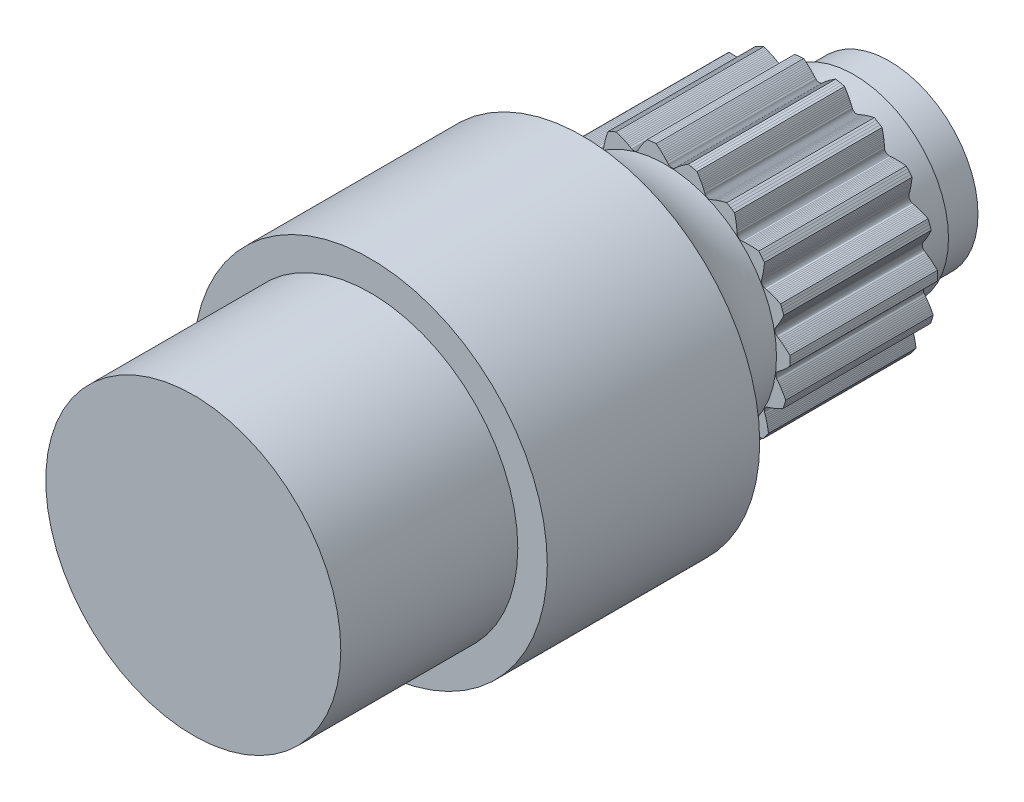
SolidWorks part; units mm, degrees
ref_plane "Front Plane" through (0, 0, 0) normal (0, 0, 1) x (1, 0, 0)
ref_plane "Top Plane" through (0, 0, 0) normal (0, 1, 0) x (1, 0, 0)
ref_plane "Right Plane" through (0, 0, 0) normal (1, 0, 0) x (0, 0, -1)
sketch "19T Shaft" plane through (0, 0, 0) normal (0, 0, 1) x (1, 0, 0)
  point P0 (-10.5755, 0)
  line B0 (6.0231, -8.6927) -> (5.8644, -8.8006)
  line B1 (5.8644, -8.8006) -> (5.7037, -8.9056)
  line B2 (5.7037, -8.9056) -> (5.5745, -8.8826)
  line B3 (5.5745, -8.8826) -> (5.4476, -8.8579)
  line B4 (5.4476, -8.8579) -> (5.3232, -8.8314)
  line B5 (5.3232, -8.8314) -> (5.1984, -8.8027)
  line B6 (5.1984, -8.8027) -> (5.0761, -8.7722)
  line B7 (5.0761, -8.7722) -> (4.9565, -8.7403)
  line B8 (4.9565, -8.7403) -> (4.8368, -8.706)
  line B9 (4.8368, -8.706) -> (4.7198, -8.6703)
  line B10 (4.7198, -8.6703) -> (4.603, -8.6323)
  line B11 (4.603, -8.6323) -> (4.4891, -8.593)
  line B12 (4.4891, -8.593) -> (4.3274, -8.5331)
  line B13 (4.3274, -8.5331) -> (4.2909, -8.5213)
  line B14 (4.2909, -8.5213) -> (4.254, -8.5136)
  line B15 (4.254, -8.5136) -> (4.2158, -8.5099)
  line B16 (4.2158, -8.5099) -> (4.1778, -8.5104)
  line B17 (4.1778, -8.5104) -> (4.1402, -8.515)
  line B18 (4.1402, -8.515) -> (4.1034, -8.5237)
  line B19 (4.1034, -8.5237) -> (4.0679, -8.5363)
  line B20 (4.0679, -8.5363) -> (4.0531, -8.5429)
  line B21 (4.0531, -8.5429) -> (4.0429, -8.5478)
  line B22 (4.0429, -8.5478) -> (4.0326, -8.5526)
  line B23 (4.0326, -8.5526) -> (4.0223, -8.5575)
  line B24 (4.0223, -8.5575) -> (4.012, -8.5623)
  line B25 (4.012, -8.5623) -> (3.9976, -8.5695)
  line B26 (3.9976, -8.5695) -> (3.9652, -8.5889)
  line B27 (3.9652, -8.5889) -> (3.9351, -8.6117)
  line B28 (3.9351, -8.6117) -> (3.9076, -8.6377)
  line B29 (3.9076, -8.6377) -> (3.883, -8.6668)
  line B30 (3.883, -8.6668) -> (3.8616, -8.6986)
  line B31 (3.8616, -8.6986) -> (3.8441, -8.732)
  line B32 (3.8441, -8.732) -> (3.83, -8.7676)
  line B33 (3.83, -8.7676) -> (3.7733, -8.9305)
  line B34 (3.7733, -8.9305) -> (3.7312, -9.0434)
  line B35 (3.7312, -9.0434) -> (3.6862, -9.1576)
  line B36 (3.6862, -9.1576) -> (3.6393, -9.2706)
  line B37 (3.6393, -9.2706) -> (3.5895, -9.3848)
  line B38 (3.5895, -9.3848) -> (3.5381, -9.4975)
  line B39 (3.5381, -9.4975) -> (3.4838, -9.6111)
  line B40 (3.4838, -9.6111) -> (3.4265, -9.7257)
  line B41 (3.4265, -9.7257) -> (3.3678, -9.8385)
  line B42 (3.3678, -9.8385) -> (3.3062, -9.9521)
  line B43 (3.3062, -9.9521) -> (3.2417, -10.0664)
  line B44 (3.2417, -10.0664) -> (3.0585, -10.1236)
  line B45 (3.0585, -10.1236) -> (2.8742, -10.1774)
  line B46 (8.5193, -6.266) -> (8.4042, -6.4196)
  line B47 (8.4042, -6.4196) -> (8.2863, -6.5711)
  line B48 (8.2863, -6.5711) -> (8.1566, -6.5913)
  line B49 (8.1566, -6.5913) -> (8.0286, -6.6091)
  line B50 (8.0286, -6.6091) -> (7.9024, -6.6245)
  line B51 (7.9024, -6.6245) -> (7.775, -6.6378)
  line B52 (7.775, -6.6378) -> (7.6495, -6.6487)
  line B53 (7.6495, -6.6487) -> (7.5259, -6.6573)
  line B54 (7.5259, -6.6573) -> (7.4015, -6.6638)
  line B55 (7.4015, -6.6638) -> (7.2793, -6.668)
  line B56 (7.2793, -6.668) -> (7.1565, -6.67)
  line B57 (7.1565, -6.67) -> (7.036, -6.6698)
  line B58 (7.036, -6.6698) -> (6.8636, -6.6657)
  line B59 (6.8636, -6.6657) -> (6.8253, -6.6663)
  line B60 (6.8253, -6.6663) -> (6.7879, -6.671)
  line B61 (6.7879, -6.671) -> (6.7506, -6.6799)
  line B62 (6.7506, -6.6799) -> (6.7147, -6.6927)
  line B63 (6.7147, -6.6927) -> (6.6807, -6.7093)
  line B64 (6.6807, -6.7093) -> (6.6487, -6.7295)
  line B65 (6.6487, -6.7295) -> (6.6192, -6.753)
  line B66 (6.6192, -6.753) -> (6.6074, -6.764)
  line B67 (6.6074, -6.764) -> (6.5993, -6.7719)
  line B68 (6.5993, -6.7719) -> (6.5911, -6.7798)
  line B69 (6.5911, -6.7798) -> (6.583, -6.7878)
  line B70 (6.583, -6.7878) -> (6.5748, -6.7957)
  line B71 (6.5748, -6.7957) -> (6.5635, -6.8072)
  line B72 (6.5635, -6.8072) -> (6.5392, -6.836)
  line B73 (6.5392, -6.836) -> (6.5181, -6.8673)
  line B74 (6.5181, -6.8673) -> (6.5006, -6.9009)
  line B75 (6.5006, -6.9009) -> (6.4867, -6.9364)
  line B76 (6.4867, -6.9364) -> (6.4768, -6.9734)
  line B77 (6.4768, -6.9734) -> (6.4711, -7.0107)
  line B78 (6.4711, -7.0107) -> (6.4693, -7.049)
  line B79 (6.4693, -7.049) -> (6.4686, -7.2215)
  line B80 (6.4686, -7.2215) -> (6.4654, -7.3419)
  line B81 (6.4654, -7.3419) -> (6.4599, -7.4646)
  line B82 (6.4599, -7.4646) -> (6.4523, -7.5866)
  line B83 (6.4523, -7.5866) -> (6.4423, -7.7108)
  line B84 (6.4423, -7.7108) -> (6.4302, -7.834)
  line B85 (6.4302, -7.834) -> (6.4157, -7.9592)
  line B86 (6.4157, -7.9592) -> (6.3988, -8.0862)
  line B87 (6.3988, -8.0862) -> (6.3799, -8.2119)
  line B88 (6.3799, -8.2119) -> (6.3585, -8.3394)
  line B89 (6.3585, -8.3394) -> (6.3346, -8.4684)
  line B90 (6.3346, -8.4684) -> (6.1799, -8.582)
  line B91 (6.1799, -8.582) -> (6.0231, -8.6927)
  line B92 (10.0923, -3.1603) -> (10.0332, -3.3429)
  line B93 (10.0332, -3.3429) -> (9.9709, -3.5245)
  line B94 (9.9709, -3.5245) -> (9.8549, -3.5857)
  line B95 (9.8549, -3.5857) -> (9.7396, -3.6441)
  line B96 (9.7396, -3.6441) -> (9.6252, -3.6997)
  line B97 (9.6252, -3.6997) -> (9.509, -3.7536)
  line B98 (9.509, -3.7536) -> (9.3938, -3.8047)
  line B99 (9.3938, -3.8047) -> (9.2797, -3.853)
  line B100 (9.2797, -3.853) -> (9.1642, -3.8995)
  line B101 (9.1642, -3.8995) -> (9.05, -3.9431)
  line B102 (9.05, -3.9431) -> (8.9345, -3.9849)
  line B103 (8.9345, -3.9849) -> (8.8205, -4.0238)
  line B104 (8.8205, -4.0238) -> (8.6561, -4.0759)
  line B105 (8.6561, -4.0759) -> (8.62, -4.089)
  line B106 (8.62, -4.089) -> (8.5862, -4.1055)
  line B107 (8.5862, -4.1055) -> (8.5538, -4.1261)
  line B108 (8.5538, -4.1261) -> (8.524, -4.1498)
  line B109 (8.524, -4.1498) -> (8.4972, -4.1766)
  line B110 (8.4972, -4.1766) -> (8.4735, -4.206)
  line B111 (8.4735, -4.206) -> (8.4533, -4.2378)
  line B112 (8.4533, -4.2378) -> (8.4457, -4.2521)
  line B113 (8.4457, -4.2521) -> (8.4405, -4.2622)
  line B114 (8.4405, -4.2622) -> (8.4354, -4.2723)
  line B115 (8.4354, -4.2723) -> (8.4303, -4.2825)
  line B116 (8.4303, -4.2825) -> (8.4251, -4.2926)
  line B117 (8.4251, -4.2926) -> (8.4181, -4.3072)
  line B118 (8.4181, -4.3072) -> (8.4045, -4.3423)
  line B119 (8.4045, -4.3423) -> (8.3948, -4.3788)
  line B120 (8.3948, -4.3788) -> (8.3891, -4.4163)
  line B121 (8.3891, -4.4163) -> (8.3875, -4.4543)
  line B122 (8.3875, -4.4543) -> (8.3902, -4.4926)
  line B123 (8.3902, -4.4926) -> (8.3968, -4.5297)
  line B124 (8.3968, -4.5297) -> (8.4076, -4.5665)
  line B125 (8.4076, -4.5665) -> (8.4629, -4.7298)
  line B126 (8.4629, -4.7298) -> (8.499, -4.8448)
  line B127 (8.499, -4.8448) -> (8.5336, -4.9626)
  line B128 (8.5336, -4.9626) -> (8.566, -5.0805)
  line B129 (8.566, -5.0805) -> (8.5969, -5.2012)
  line B130 (8.5969, -5.2012) -> (8.6255, -5.3217)
  line B131 (8.6255, -5.3217) -> (8.6525, -5.4448)
  line B132 (8.6525, -5.4448) -> (8.6777, -5.5704)
  line B133 (8.6777, -5.5704) -> (8.7006, -5.6954)
  line B134 (8.7006, -5.6954) -> (8.7218, -5.8229)
  line B135 (8.7218, -5.8229) -> (8.7411, -5.9527)
  line B136 (8.7411, -5.9527) -> (8.6316, -6.1104)
  line B137 (8.6316, -6.1104) -> (8.5193, -6.266)
  line B138 (10.5716, 0.2879) -> (10.5751, 0.096)
  line B139 (10.5751, 0.096) -> (10.5751, -0.096)
  line B140 (10.5751, -0.096) -> (10.4852, -0.1916)
  line B141 (10.4852, -0.1916) -> (10.3951, -0.2842)
  line B142 (10.3951, -0.2842) -> (10.3049, -0.3739)
  line B143 (10.3049, -0.3739) -> (10.2126, -0.4627)
  line B144 (10.2126, -0.4627) -> (10.1202, -0.5484)
  line B145 (10.1202, -0.5484) -> (10.028, -0.6311)
  line B146 (10.028, -0.6311) -> (9.9338, -0.7126)
  line B147 (9.9338, -0.7126) -> (9.8399, -0.791)
  line B148 (9.8399, -0.791) -> (9.7443, -0.868)
  line B149 (9.7443, -0.868) -> (9.6491, -0.9418)
  line B150 (9.6491, -0.9418) -> (9.5105, -1.0445)
  line B151 (9.5105, -1.0445) -> (9.4807, -1.0685)
  line B152 (9.4807, -1.0685) -> (9.454, -1.0952)
  line B153 (9.454, -1.0952) -> (9.43, -1.1251)
  line B154 (9.43, -1.1251) -> (9.4096, -1.1573)
  line B155 (9.4096, -1.1573) -> (9.3929, -1.1913)
  line B156 (9.3929, -1.1913) -> (9.3801, -1.2268)
  line B157 (9.3801, -1.2268) -> (9.3712, -1.2634)
  line B158 (9.3712, -1.2634) -> (9.3687, -1.2794)
  line B159 (9.3687, -1.2794) -> (9.3671, -1.2906)
  line B160 (9.3671, -1.2906) -> (9.3656, -1.3019)
  line B161 (9.3656, -1.3019) -> (9.364, -1.3131)
  line B162 (9.364, -1.3131) -> (9.3624, -1.3244)
  line B163 (9.3624, -1.3244) -> (9.3605, -1.3404)
  line B164 (9.3605, -1.3404) -> (9.3591, -1.3781)
  line B165 (9.3591, -1.3781) -> (9.3617, -1.4158)
  line B166 (9.3617, -1.4158) -> (9.3685, -1.4531)
  line B167 (9.3685, -1.4531) -> (9.3794, -1.4895)
  line B168 (9.3794, -1.4895) -> (9.3943, -1.5249)
  line B169 (9.3943, -1.5249) -> (9.4126, -1.5578)
  line B170 (9.4126, -1.5578) -> (9.4348, -1.5891)
  line B171 (9.4348, -1.5891) -> (9.5401, -1.7256)
  line B172 (9.5401, -1.7256) -> (9.6116, -1.8226)
  line B173 (9.6116, -1.8226) -> (9.6826, -1.9228)
  line B174 (9.6826, -1.9228) -> (9.7515, -2.0239)
  line B175 (9.7515, -2.0239) -> (9.8199, -2.128)
  line B176 (9.8199, -2.128) -> (9.8861, -2.2327)
  line B177 (9.8861, -2.2327) -> (9.9516, -2.3403)
  line B178 (9.9516, -2.3403) -> (10.0162, -2.4509)
  line B179 (10.0162, -2.4509) -> (10.0785, -2.5618)
  line B180 (10.0785, -2.5618) -> (10.1399, -2.6755)
  line B181 (10.1399, -2.6755) -> (10.2003, -2.792)
  line B182 (10.2003, -2.792) -> (10.1479, -2.9766)
  line B183 (10.1479, -2.9766) -> (10.0923, -3.1603)
  line B184 (9.9053, 3.7049) -> (9.9709, 3.5245)
  line B185 (9.9709, 3.5245) -> (10.0332, 3.3429)
  line B186 (10.0332, 3.3429) -> (9.9793, 3.2233)
  line B187 (9.9793, 3.2233) -> (9.9242, 3.1065)
  line B188 (9.9242, 3.1065) -> (9.868, 2.9924)
  line B189 (9.868, 2.9924) -> (9.8094, 2.8784)
  line B190 (9.8094, 2.8784) -> (9.7499, 2.7674)
  line B191 (9.7499, 2.7674) -> (9.6896, 2.6592)
  line B192 (9.6896, 2.6592) -> (9.627, 2.5516)
  line B193 (9.627, 2.5516) -> (9.5636, 2.4469)
  line B194 (9.5636, 2.4469) -> (9.4981, 2.343)
  line B195 (9.4981, 2.343) -> (9.4321, 2.2423)
  line B196 (9.4321, 2.2423) -> (9.3343, 2.1002)
  line B197 (9.3343, 2.1002) -> (9.3139, 2.0678)
  line B198 (9.3139, 2.0678) -> (9.2974, 2.0339)
  line B199 (9.2974, 2.0339) -> (9.2844, 1.9978)
  line B200 (9.2844, 1.9978) -> (9.2755, 1.9607)
  line B201 (9.2755, 1.9607) -> (9.2708, 1.9232)
  line B202 (9.2708, 1.9232) -> (9.2702, 1.8854)
  line B203 (9.2702, 1.8854) -> (9.2737, 1.8479)
  line B204 (9.2737, 1.8479) -> (9.2765, 1.832)
  line B205 (9.2765, 1.832) -> (9.2787, 1.8208)
  line B206 (9.2787, 1.8208) -> (9.2809, 1.8097)
  line B207 (9.2809, 1.8097) -> (9.283, 1.7985)
  line B208 (9.283, 1.7985) -> (9.2852, 1.7873)
  line B209 (9.2852, 1.7873) -> (9.2886, 1.7716)
  line B210 (9.2886, 1.7716) -> (9.2994, 1.7354)
  line B211 (9.2994, 1.7354) -> (9.3142, 1.7007)
  line B212 (9.3142, 1.7007) -> (9.3327, 1.6676)
  line B213 (9.3327, 1.6676) -> (9.3548, 1.6366)
  line B214 (9.3548, 1.6366) -> (9.3804, 1.6081)
  line B215 (9.3804, 1.6081) -> (9.4085, 1.5829)
  line B216 (9.4085, 1.5829) -> (9.4396, 1.5605)
  line B217 (9.4396, 1.5605) -> (9.5835, 1.4655)
  line B218 (9.5835, 1.4655) -> (9.6826, 1.397)
  line B219 (9.6826, 1.397) -> (9.7823, 1.3253)
  line B220 (9.7823, 1.3253) -> (9.8803, 1.2521)
  line B221 (9.8803, 1.2521) -> (9.9788, 1.1759)
  line B222 (9.9788, 1.1759) -> (10.0754, 1.0983)
  line B223 (10.0754, 1.0983) -> (10.1722, 1.0178)
  line B224 (10.1722, 1.0178) -> (10.2693, 0.9342)
  line B225 (10.2693, 0.9342) -> (10.3642, 0.8495)
  line B226 (10.3642, 0.8495) -> (10.4592, 0.7619)
  line B227 (10.4592, 0.7619) -> (10.5542, 0.6713)
  line B228 (10.5542, 0.6713) -> (10.5646, 0.4797)
  line B229 (10.5646, 0.4797) -> (10.5716, 0.2879)
  line B230 (8.1656, 6.7204) -> (8.2863, 6.5711)
  line B231 (8.2863, 6.5711) -> (8.4042, 6.4196)
  line B232 (8.4042, 6.4196) -> (8.392, 6.2889)
  line B233 (8.392, 6.2889) -> (8.3778, 6.1605)
  line B234 (8.3778, 6.1605) -> (8.3617, 6.0344)
  line B235 (8.3617, 6.0344) -> (8.3433, 5.9076)
  line B236 (8.3433, 5.9076) -> (8.3231, 5.7832)
  line B237 (8.3231, 5.7832) -> (8.3011, 5.6613)
  line B238 (8.3011, 5.6613) -> (8.2769, 5.5392)
  line B239 (8.2769, 5.5392) -> (8.2509, 5.4196)
  line B240 (8.2509, 5.4196) -> (8.2227, 5.3001)
  line B241 (8.2227, 5.3001) -> (8.193, 5.1834)
  line B242 (8.193, 5.1834) -> (8.1466, 5.0172)
  line B243 (8.1466, 5.0172) -> (8.1379, 4.9799)
  line B244 (8.1379, 4.9799) -> (8.1332, 4.9425)
  line B245 (8.1332, 4.9425) -> (8.1327, 4.9042)
  line B246 (8.1327, 4.9042) -> (8.1363, 4.8663)
  line B247 (8.1363, 4.8663) -> (8.144, 4.8292)
  line B248 (8.144, 4.8292) -> (8.1557, 4.7933)
  line B249 (8.1557, 4.7933) -> (8.1712, 4.7589)
  line B250 (8.1712, 4.7589) -> (8.179, 4.7448)
  line B251 (8.179, 4.7448) -> (8.1847, 4.7349)
  line B252 (8.1847, 4.7349) -> (8.1904, 4.7251)
  line B253 (8.1904, 4.7251) -> (8.1961, 4.7152)
  line B254 (8.1961, 4.7152) -> (8.2017, 4.7054)
  line B255 (8.2017, 4.7054) -> (8.2101, 4.6916)
  line B256 (8.2101, 4.6916) -> (8.2321, 4.6609)
  line B257 (8.2321, 4.6609) -> (8.2573, 4.6328)
  line B258 (8.2573, 4.6328) -> (8.2855, 4.6076)
  line B259 (8.2855, 4.6076) -> (8.3165, 4.5855)
  line B260 (8.3165, 4.5855) -> (8.35, 4.5667)
  line B261 (8.35, 4.5667) -> (8.3847, 4.552)
  line B262 (8.3847, 4.552) -> (8.4214, 4.541)
  line B263 (8.4214, 4.541) -> (8.5884, 4.4979)
  line B264 (8.5884, 4.4979) -> (8.7044, 4.4652)
  line B265 (8.7044, 4.4652) -> (8.822, 4.4298)
  line B266 (8.822, 4.4298) -> (8.9384, 4.3924)
  line B267 (8.9384, 4.3924) -> (9.0563, 4.3523)
  line B268 (9.0563, 4.3523) -> (9.1728, 4.3103)
  line B269 (9.1728, 4.3103) -> (9.2906, 4.2655)
  line B270 (9.2906, 4.2655) -> (9.4096, 4.218)
  line B271 (9.4096, 4.218) -> (9.5268, 4.1688)
  line B272 (9.5268, 4.1688) -> (9.6451, 4.1167)
  line B273 (9.6451, 4.1167) -> (9.7643, 4.0619)
  line B274 (9.7643, 4.0619) -> (9.8364, 3.884)
  line B275 (9.8364, 3.884) -> (9.9053, 3.7049)
  line B276 (5.5411, 9.0076) -> (5.7037, 8.9056)
  line B277 (5.7037, 8.9056) -> (5.8644, 8.8006)
  line B278 (5.8644, 8.8006) -> (5.8952, 8.6731)
  line B279 (5.8952, 8.6731) -> (5.9235, 8.547)
  line B280 (5.9235, 8.547) -> (5.9493, 8.4224)
  line B281 (5.9493, 8.4224) -> (5.9731, 8.2966)
  line B282 (5.9731, 8.2966) -> (5.9943, 8.1724)
  line B283 (5.9943, 8.1724) -> (6.0131, 8.0499)
  line B284 (6.0131, 8.0499) -> (6.0298, 7.9265)
  line B285 (6.0298, 7.9265) -> (6.0441, 7.8051)
  line B286 (6.0441, 7.8051) -> (6.0563, 7.6829)
  line B287 (6.0563, 7.6829) -> (6.066, 7.5628)
  line B288 (6.066, 7.5628) -> (6.0761, 7.3906)
  line B289 (6.0761, 7.3906) -> (6.0799, 7.3525)
  line B290 (6.0799, 7.3525) -> (6.0877, 7.3156)
  line B291 (6.0877, 7.3156) -> (6.0996, 7.2791)
  line B292 (6.0996, 7.2791) -> (6.1154, 7.2445)
  line B293 (6.1154, 7.2445) -> (6.1347, 7.2119)
  line B294 (6.1347, 7.2119) -> (6.1575, 7.1817)
  line B295 (6.1575, 7.1817) -> (6.1833, 7.1543)
  line B296 (6.1833, 7.1543) -> (6.1952, 7.1434)
  line B297 (6.1952, 7.1434) -> (6.2038, 7.1359)
  line B298 (6.2038, 7.1359) -> (6.2124, 7.1285)
  line B299 (6.2124, 7.1285) -> (6.221, 7.121)
  line B300 (6.221, 7.121) -> (6.2295, 7.1135)
  line B301 (6.2295, 7.1135) -> (6.2419, 7.1032)
  line B302 (6.2419, 7.1032) -> (6.2726, 7.0813)
  line B303 (6.2726, 7.0813) -> (6.3056, 7.063)
  line B304 (6.3056, 7.063) -> (6.3405, 7.0482)
  line B305 (6.3405, 7.0482) -> (6.377, 7.0374)
  line B306 (6.377, 7.0374) -> (6.4148, 7.0305)
  line B307 (6.4148, 7.0305) -> (6.4524, 7.0279)
  line B308 (6.4524, 7.0279) -> (6.4907, 7.0293)
  line B309 (6.4907, 7.0293) -> (6.6626, 7.0428)
  line B310 (6.6626, 7.0428) -> (6.7829, 7.0496)
  line B311 (6.7829, 7.0496) -> (6.9056, 7.0543)
  line B312 (6.9056, 7.0543) -> (7.0279, 7.0567)
  line B313 (7.0279, 7.0567) -> (7.1524, 7.057)
  line B314 (7.1524, 7.057) -> (7.2763, 7.0552)
  line B315 (7.2763, 7.0552) -> (7.4022, 7.0511)
  line B316 (7.4022, 7.0511) -> (7.5302, 7.0447)
  line B317 (7.5302, 7.0447) -> (7.657, 7.0362)
  line B318 (7.657, 7.0362) -> (7.7858, 7.0255)
  line B319 (7.7858, 7.0255) -> (7.9164, 7.0123)
  line B320 (7.9164, 7.0123) -> (8.0423, 6.8675)
  line B321 (8.0423, 6.8675) -> (8.1656, 6.7204)
  line B322 (2.3161, 10.3188) -> (2.503, 10.275)
  line B323 (2.503, 10.275) -> (2.6891, 10.2279)
  line B324 (2.6891, 10.2279) -> (2.7597, 10.1173)
  line B325 (2.7597, 10.1173) -> (2.8274, 10.0073)
  line B326 (2.8274, 10.0073) -> (2.8922, 9.8978)
  line B327 (2.8922, 9.8978) -> (2.9555, 9.7865)
  line B328 (2.9555, 9.7865) -> (3.016, 9.6759)
  line B329 (3.016, 9.6759) -> (3.0735, 9.5662)
  line B330 (3.0735, 9.5662) -> (3.1294, 9.4549)
  line B331 (3.1294, 9.4549) -> (3.1823, 9.3447)
  line B332 (3.1823, 9.3447) -> (3.2335, 9.233)
  line B333 (3.2335, 9.233) -> (3.2817, 9.1226)
  line B334 (3.2817, 9.1226) -> (3.3472, 8.9631)
  line B335 (3.3472, 8.9631) -> (3.3632, 8.9283)
  line B336 (3.3632, 8.9283) -> (3.3825, 8.8959)
  line B337 (3.3825, 8.8959) -> (3.4056, 8.8653)
  line B338 (3.4056, 8.8653) -> (3.4318, 8.8376)
  line B339 (3.4318, 8.8376) -> (3.4606, 8.8131)
  line B340 (3.4606, 8.8131) -> (3.4919, 8.7919)
  line B341 (3.4919, 8.7919) -> (3.5253, 8.7743)
  line B342 (3.5253, 8.7743) -> (3.5401, 8.7679)
  line B343 (3.5401, 8.7679) -> (3.5506, 8.7637)
  line B344 (3.5506, 8.7637) -> (3.5612, 8.7594)
  line B345 (3.5612, 8.7594) -> (3.5717, 8.7551)
  line B346 (3.5717, 8.7551) -> (3.5822, 8.7508)
  line B347 (3.5822, 8.7508) -> (3.5973, 8.7451)
  line B348 (3.5973, 8.7451) -> (3.6335, 8.7344)
  line B349 (3.6335, 8.7344) -> (3.6706, 8.7277)
  line B350 (3.6706, 8.7277) -> (3.7084, 8.7251)
  line B351 (3.7084, 8.7251) -> (3.7465, 8.7267)
  line B352 (3.7465, 8.7267) -> (3.7844, 8.7325)
  line B353 (3.7844, 8.7325) -> (3.8208, 8.7422)
  line B354 (3.8208, 8.7422) -> (3.8566, 8.756)
  line B355 (3.8566, 8.756) -> (4.0148, 8.8246)
  line B356 (4.0148, 8.8246) -> (4.1264, 8.87)
  line B357 (4.1264, 8.87) -> (4.2409, 8.9143)
  line B358 (4.2409, 8.9143) -> (4.3558, 8.9563)
  line B359 (4.3558, 8.9563) -> (4.4735, 8.997)
  line B360 (4.4735, 8.997) -> (4.5912, 9.0355)
  line B361 (4.5912, 9.0355) -> (4.7116, 9.0725)
  line B362 (4.7116, 9.0725) -> (4.8347, 9.1081)
  line B363 (4.8347, 9.1081) -> (4.9575, 9.1412)
  line B364 (4.9575, 9.1412) -> (5.0828, 9.1728)
  line B365 (5.0828, 9.1728) -> (5.2106, 9.2028)
  line B366 (5.2106, 9.2028) -> (5.3767, 9.1067)
  line B367 (5.3767, 9.1067) -> (5.5411, 9.0076)
  line B368 (-1.1599, 10.5117) -> (-0.9689, 10.531)
  line B369 (-0.9689, 10.531) -> (-0.7776, 10.5469)
  line B370 (-0.7776, 10.5469) -> (-0.6749, 10.4652)
  line B371 (-0.6749, 10.4652) -> (-0.5752, 10.3831)
  line B372 (-0.5752, 10.3831) -> (-0.4783, 10.3006)
  line B373 (-0.4783, 10.3006) -> (-0.3823, 10.2159)
  line B374 (-0.3823, 10.2159) -> (-0.2892, 10.1309)
  line B375 (-0.2892, 10.1309) -> (-0.1992, 10.0459)
  line B376 (-0.1992, 10.0459) -> (-0.1102, 9.9587)
  line B377 (-0.1102, 9.9587) -> (-0.0243, 9.8716)
  line B378 (-0.0243, 9.8716) -> (0.0603, 9.7827)
  line B379 (0.0603, 9.7827) -> (0.1418, 9.6939)
  line B380 (0.1418, 9.6939) -> (0.2555, 9.5643)
  line B381 (0.2555, 9.5643) -> (0.2819, 9.5365)
  line B382 (0.2819, 9.5365) -> (0.3107, 9.5122)
  line B383 (0.3107, 9.5122) -> (0.3425, 9.4907)
  line B384 (0.3425, 9.4907) -> (0.3763, 9.473)
  line B385 (0.3763, 9.473) -> (0.4115, 9.4592)
  line B386 (0.4115, 9.4592) -> (0.448, 9.4494)
  line B387 (0.448, 9.4494) -> (0.4852, 9.4436)
  line B388 (0.4852, 9.4436) -> (0.5013, 9.4423)
  line B389 (0.5013, 9.4423) -> (0.5127, 9.4417)
  line B390 (0.5127, 9.4417) -> (0.524, 9.4411)
  line B391 (0.524, 9.4411) -> (0.5354, 9.4405)
  line B392 (0.5354, 9.4405) -> (0.5467, 9.4398)
  line B393 (0.5467, 9.4398) -> (0.5629, 9.4393)
  line B394 (0.5629, 9.4393) -> (0.6005, 9.4409)
  line B395 (0.6005, 9.4409) -> (0.6379, 9.4467)
  line B396 (0.6379, 9.4467) -> (0.6744, 9.4565)
  line B397 (0.6744, 9.4565) -> (0.7099, 9.4703)
  line B398 (0.7099, 9.4703) -> (0.7439, 9.4881)
  line B399 (0.7439, 9.4881) -> (0.7752, 9.5091)
  line B400 (0.7752, 9.5091) -> (0.8045, 9.5338)
  line B401 (0.8045, 9.5338) -> (0.9319, 9.6501)
  line B402 (0.9319, 9.6501) -> (1.0227, 9.7293)
  line B403 (1.0227, 9.7293) -> (1.1167, 9.8083)
  line B404 (1.1167, 9.8083) -> (1.2117, 9.8854)
  line B405 (1.2117, 9.8854) -> (1.3098, 9.9621)
  line B406 (1.3098, 9.9621) -> (1.4086, 10.0367)
  line B407 (1.4086, 10.0367) -> (1.5105, 10.1108)
  line B408 (1.5105, 10.1108) -> (1.6154, 10.1844)
  line B409 (1.6154, 10.1844) -> (1.7207, 10.2556)
  line B410 (1.7207, 10.2556) -> (1.829, 10.3262)
  line B411 (1.829, 10.3262) -> (1.9401, 10.396)
  line B412 (1.9401, 10.396) -> (2.1285, 10.3591)
  line B413 (2.1285, 10.3591) -> (2.3161, 10.3188)
  line B414 (-4.5102, 9.5655) -> (-4.3358, 9.6458)
  line B415 (-4.3358, 9.6458) -> (-4.1601, 9.7229)
  line B416 (-4.1601, 9.7229) -> (-4.0364, 9.679)
  line B417 (-4.0364, 9.679) -> (-3.9154, 9.6337)
  line B418 (-3.9154, 9.6337) -> (-3.797, 9.5872)
  line B419 (-3.797, 9.5872) -> (-3.6786, 9.5382)
  line B420 (-3.6786, 9.5382) -> (-3.5631, 9.4881)
  line B421 (-3.5631, 9.4881) -> (-3.4503, 9.4369)
  line B422 (-3.4503, 9.4369) -> (-3.3378, 9.3834)
  line B423 (-3.3378, 9.3834) -> (-3.2283, 9.3289)
  line B424 (-3.2283, 9.3289) -> (-3.1194, 9.2722)
  line B425 (-3.1194, 9.2722) -> (-3.0135, 9.2147)
  line B426 (-3.0135, 9.2147) -> (-2.8638, 9.129)
  line B427 (-2.8638, 9.129) -> (-2.8298, 9.1113)
  line B428 (-2.8298, 9.1113) -> (-2.7947, 9.0977)
  line B429 (-2.7947, 9.0977) -> (-2.7577, 9.0877)
  line B430 (-2.7577, 9.0877) -> (-2.72, 9.0819)
  line B431 (-2.72, 9.0819) -> (-2.6822, 9.0803)
  line B432 (-2.6822, 9.0803) -> (-2.6445, 9.0828)
  line B433 (-2.6445, 9.0828) -> (-2.6074, 9.0894)
  line B434 (-2.6074, 9.0894) -> (-2.5917, 9.0935)
  line B435 (-2.5917, 9.0935) -> (-2.5808, 9.0966)
  line B436 (-2.5808, 9.0966) -> (-2.5699, 9.0997)
  line B437 (-2.5699, 9.0997) -> (-2.5589, 9.1028)
  line B438 (-2.5589, 9.1028) -> (-2.548, 9.1059)
  line B439 (-2.548, 9.1059) -> (-2.5325, 9.1106)
  line B440 (-2.5325, 9.1106) -> (-2.4975, 9.1244)
  line B441 (-2.4975, 9.1244) -> (-2.464, 9.1419)
  line B442 (-2.464, 9.1419) -> (-2.4326, 9.1631)
  line B443 (-2.4326, 9.1631) -> (-2.4036, 9.1877)
  line B444 (-2.4036, 9.1877) -> (-2.3772, 9.2156)
  line B445 (-2.3772, 9.2156) -> (-2.3544, 9.2456)
  line B446 (-2.3544, 9.2456) -> (-2.3347, 9.2785)
  line B447 (-2.3347, 9.2785) -> (-2.2519, 9.4298)
  line B448 (-2.2519, 9.4298) -> (-2.1918, 9.5342)
  line B449 (-2.1918, 9.5342) -> (-2.1286, 9.6395)
  line B450 (-2.1286, 9.6395) -> (-2.0638, 9.7432)
  line B451 (-2.0638, 9.7432) -> (-1.9959, 9.8476)
  line B452 (-1.9959, 9.8476) -> (-1.9266, 9.9503)
  line B453 (-1.9266, 9.9503) -> (-1.8543, 10.0535)
  line B454 (-1.8543, 10.0535) -> (-1.779, 10.1571)
  line B455 (-1.779, 10.1571) -> (-1.7025, 10.2587)
  line B456 (-1.7025, 10.2587) -> (-1.623, 10.3606)
  line B457 (-1.623, 10.3606) -> (-1.5406, 10.4627)
  line B458 (-1.5406, 10.4627) -> (-1.3505, 10.4889)
  line B459 (-1.3505, 10.4889) -> (-1.1599, 10.5117)
  line B460 (-7.3717, 7.5828) -> (-7.2329, 7.7153)
  line B461 (-7.2329, 7.7153) -> (-7.0917, 7.8453)
  line B462 (-7.0917, 7.8453) -> (-6.9605, 7.844)
  line B463 (-6.9605, 7.844) -> (-6.8313, 7.8404)
  line B464 (-6.8313, 7.8404) -> (-6.7042, 7.8348)
  line B465 (-6.7042, 7.8348) -> (-6.5764, 7.827)
  line B466 (-6.5764, 7.827) -> (-6.4508, 7.8171)
  line B467 (-6.4508, 7.8171) -> (-6.3275, 7.8052)
  line B468 (-6.3275, 7.8052) -> (-6.2037, 7.7912)
  line B469 (-6.2037, 7.7912) -> (-6.0825, 7.7752)
  line B470 (-6.0825, 7.7752) -> (-5.961, 7.757)
  line B471 (-5.961, 7.757) -> (-5.8422, 7.7369)
  line B472 (-5.8422, 7.7369) -> (-5.6729, 7.7045)
  line B473 (-5.6729, 7.7045) -> (-5.635, 7.6988)
  line B474 (-5.635, 7.6988) -> (-5.5973, 7.6973)
  line B475 (-5.5973, 7.6973) -> (-5.559, 7.6999)
  line B476 (-5.559, 7.6999) -> (-5.5215, 7.7067)
  line B477 (-5.5215, 7.7067) -> (-5.4852, 7.7174)
  line B478 (-5.4852, 7.7174) -> (-5.4504, 7.732)
  line B479 (-5.4504, 7.732) -> (-5.4174, 7.7503)
  line B480 (-5.4174, 7.7503) -> (-5.404, 7.7593)
  line B481 (-5.404, 7.7593) -> (-5.3946, 7.7658)
  line B482 (-5.3946, 7.7658) -> (-5.3853, 7.7722)
  line B483 (-5.3853, 7.7722) -> (-5.376, 7.7787)
  line B484 (-5.376, 7.7787) -> (-5.3666, 7.7852)
  line B485 (-5.3666, 7.7852) -> (-5.3535, 7.7946)
  line B486 (-5.3535, 7.7946) -> (-5.3248, 7.8191)
  line B487 (-5.3248, 7.8191) -> (-5.2989, 7.8465)
  line B488 (-5.2989, 7.8465) -> (-5.2761, 7.8768)
  line B489 (-5.2761, 7.8768) -> (-5.2566, 7.9095)
  line B490 (-5.2566, 7.9095) -> (-5.2407, 7.9444)
  line B491 (-5.2407, 7.9444) -> (-5.2289, 7.9802)
  line B492 (-5.2289, 7.9802) -> (-5.2209, 8.0177)
  line B493 (-5.2209, 8.0177) -> (-5.1918, 8.1877)
  line B494 (-5.1918, 8.1877) -> (-5.1688, 8.3059)
  line B495 (-5.1688, 8.3059) -> (-5.1432, 8.426)
  line B496 (-5.1432, 8.426) -> (-5.1155, 8.5452)
  line B497 (-5.1155, 8.5452) -> (-5.0853, 8.666)
  line B498 (-5.0853, 8.666) -> (-5.0531, 8.7856)
  line B499 (-5.0531, 8.7856) -> (-5.0182, 8.9066)
  line B500 (-5.0182, 8.9066) -> (-4.9806, 9.0291)
  line B501 (-4.9806, 9.0291) -> (-4.9412, 9.15)
  line B502 (-4.9412, 9.15) -> (-4.8992, 9.2722)
  line B503 (-4.8992, 9.2722) -> (-4.8544, 9.3956)
  line B504 (-4.8544, 9.3956) -> (-4.683, 9.4821)
  line B505 (-4.683, 9.4821) -> (-4.5102, 9.5655)
  line B506 (-9.4344, 4.7783) -> (-9.3462, 4.9488)
  line B507 (-9.3462, 4.9488) -> (-9.2548, 5.1176)
  line B508 (-9.2548, 5.1176) -> (-9.1303, 5.1589)
  line B509 (-9.1303, 5.1589) -> (-9.007, 5.1975)
  line B510 (-9.007, 5.1975) -> (-8.885, 5.2334)
  line B511 (-8.885, 5.2334) -> (-8.7615, 5.2675)
  line B512 (-8.7615, 5.2675) -> (-8.6395, 5.299)
  line B513 (-8.6395, 5.299) -> (-8.519, 5.3278)
  line B514 (-8.519, 5.3278) -> (-8.3974, 5.3547)
  line B515 (-8.3974, 5.3547) -> (-8.2775, 5.3789)
  line B516 (-8.2775, 5.3789) -> (-8.1567, 5.4011)
  line B517 (-8.1567, 5.4011) -> (-8.0379, 5.4208)
  line B518 (-8.0379, 5.4208) -> (-7.8671, 5.4451)
  line B519 (-7.8671, 5.4451) -> (-7.8294, 5.452)
  line B520 (-7.8294, 5.452) -> (-7.7933, 5.4628)
  line B521 (-7.7933, 5.4628) -> (-7.758, 5.4777)
  line B522 (-7.758, 5.4777) -> (-7.7247, 5.4963)
  line B523 (-7.7247, 5.4963) -> (-7.6939, 5.5182)
  line B524 (-7.6939, 5.5182) -> (-7.6657, 5.5434)
  line B525 (-7.6657, 5.5434) -> (-7.6404, 5.5714)
  line B526 (-7.6404, 5.5714) -> (-7.6306, 5.5842)
  line B527 (-7.6306, 5.5842) -> (-7.6239, 5.5933)
  line B528 (-7.6239, 5.5933) -> (-7.6172, 5.6025)
  line B529 (-7.6172, 5.6025) -> (-7.6104, 5.6117)
  line B530 (-7.6104, 5.6117) -> (-7.6037, 5.6208)
  line B531 (-7.6037, 5.6208) -> (-7.5944, 5.634)
  line B532 (-7.5944, 5.634) -> (-7.5751, 5.6664)
  line B533 (-7.5751, 5.6664) -> (-7.5596, 5.7008)
  line B534 (-7.5596, 5.7008) -> (-7.5478, 5.7368)
  line B535 (-7.5478, 5.7368) -> (-7.54, 5.7741)
  line B536 (-7.54, 5.7741) -> (-7.5363, 5.8123)
  line B537 (-7.5363, 5.8123) -> (-7.5367, 5.85)
  line B538 (-7.5367, 5.85) -> (-7.5413, 5.888)
  line B539 (-7.5413, 5.888) -> (-7.569, 6.0583)
  line B540 (-7.569, 6.0583) -> (-7.5856, 6.1776)
  line B541 (-7.5856, 6.1776) -> (-7.6004, 6.2995)
  line B542 (-7.6004, 6.2995) -> (-7.613, 6.4212)
  line B543 (-7.613, 6.4212) -> (-7.6236, 6.5452)
  line B544 (-7.6236, 6.5452) -> (-7.6319, 6.6688)
  line B545 (-7.6319, 6.6688) -> (-7.6383, 6.7946)
  line B546 (-7.6383, 6.7946) -> (-7.6425, 6.9227)
  line B547 (-7.6425, 6.9227) -> (-7.6445, 7.0498)
  line B548 (-7.6445, 7.0498) -> (-7.6444, 7.1791)
  line B549 (-7.6444, 7.1791) -> (-7.6421, 7.3103)
  line B550 (-7.6421, 7.3103) -> (-7.5081, 7.4478)
  line B551 (-7.5081, 7.4478) -> (-7.3717, 7.5828)
  line B552 (-10.4748, 1.4561) -> (-10.4466, 1.6459)
  line B553 (-10.4466, 1.6459) -> (-10.415, 1.8353)
  line B554 (-10.415, 1.8353) -> (-10.3106, 1.9148)
  line B555 (-10.3106, 1.9148) -> (-10.2066, 1.9913)
  line B556 (-10.2066, 1.9913) -> (-10.1028, 2.0649)
  line B557 (-10.1028, 2.0649) -> (-9.9971, 2.1373)
  line B558 (-9.9971, 2.1373) -> (-9.8919, 2.2066)
  line B559 (-9.8919, 2.2066) -> (-9.7874, 2.273)
  line B560 (-9.7874, 2.273) -> (-9.6811, 2.3379)
  line B561 (-9.6811, 2.3379) -> (-9.5755, 2.3998)
  line B562 (-9.5755, 2.3998) -> (-9.4685, 2.46)
  line B563 (-9.4685, 2.46) -> (-9.3625, 2.5172)
  line B564 (-9.3625, 2.5172) -> (-9.2089, 2.5956)
  line B565 (-9.2089, 2.5956) -> (-9.1755, 2.6144)
  line B566 (-9.1755, 2.6144) -> (-9.1448, 2.6363)
  line B567 (-9.1448, 2.6363) -> (-9.1162, 2.6619)
  line B568 (-9.1162, 2.6619) -> (-9.0908, 2.6902)
  line B569 (-9.0908, 2.6902) -> (-9.0687, 2.721)
  line B570 (-9.0687, 2.721) -> (-9.0503, 2.754)
  line B571 (-9.0503, 2.754) -> (-9.0355, 2.7886)
  line B572 (-9.0355, 2.7886) -> (-9.0303, 2.804)
  line B573 (-9.0303, 2.804) -> (-9.027, 2.8148)
  line B574 (-9.027, 2.8148) -> (-9.0236, 2.8257)
  line B575 (-9.0236, 2.8257) -> (-9.0202, 2.8365)
  line B576 (-9.0202, 2.8365) -> (-9.0167, 2.8473)
  line B577 (-9.0167, 2.8473) -> (-9.0122, 2.8629)
  line B578 (-9.0122, 2.8629) -> (-9.0046, 2.8998)
  line B579 (-9.0046, 2.8998) -> (-9.001, 2.9374)
  line B580 (-9.001, 2.9374) -> (-9.0016, 2.9752)
  line B581 (-9.0016, 2.9752) -> (-9.0063, 3.013)
  line B582 (-9.0063, 3.013) -> (-9.0152, 3.0503)
  line B583 (-9.0152, 3.0503) -> (-9.0279, 3.0858)
  line B584 (-9.0279, 3.0858) -> (-9.0446, 3.1203)
  line B585 (-9.0446, 3.1203) -> (-9.126, 3.2724)
  line B586 (-9.126, 3.2724) -> (-9.1805, 3.3798)
  line B587 (-9.1805, 3.3798) -> (-9.2341, 3.4903)
  line B588 (-9.2341, 3.4903) -> (-9.2854, 3.6013)
  line B589 (-9.2854, 3.6013) -> (-9.3357, 3.7152)
  line B590 (-9.3357, 3.7152) -> (-9.3838, 3.8294)
  line B591 (-9.3838, 3.8294) -> (-9.4306, 3.9463)
  line B592 (-9.4306, 3.9463) -> (-9.4762, 4.0661)
  line B593 (-9.4762, 4.0661) -> (-9.5194, 4.1857)
  line B594 (-9.5194, 4.1857) -> (-9.5612, 4.3079)
  line B595 (-9.5612, 4.3079) -> (-9.6016, 4.4328)
  line B596 (-9.6016, 4.4328) -> (-9.5196, 4.6063)
  line B597 (-9.5196, 4.6063) -> (-9.4344, 4.7783)
  line B598 (-10.38, -2.024) -> (-10.415, -1.8353)
  line B599 (-10.415, -1.8353) -> (-10.4466, -1.6459)
  line B600 (-10.4466, -1.6459) -> (-10.3737, -1.5368)
  line B601 (-10.3737, -1.5368) -> (-10.3001, -1.4306)
  line B602 (-10.3001, -1.4306) -> (-10.2259, -1.3273)
  line B603 (-10.2259, -1.3273) -> (-10.1494, -1.2246)
  line B604 (-10.1494, -1.2246) -> (-10.0725, -1.1248)
  line B605 (-10.0725, -1.1248) -> (-9.9951, -1.0281)
  line B606 (-9.9951, -1.0281) -> (-9.9156, -0.9322)
  line B607 (-9.9156, -0.9322) -> (-9.8359, -0.8394)
  line B608 (-9.8359, -0.8394) -> (-9.7543, -0.7477)
  line B609 (-9.7543, -0.7477) -> (-9.6725, -0.6592)
  line B610 (-9.6725, -0.6592) -> (-9.5527, -0.5352)
  line B611 (-9.5527, -0.5352) -> (-9.5272, -0.5065)
  line B612 (-9.5272, -0.5065) -> (-9.5053, -0.4758)
  line B613 (-9.5053, -0.4758) -> (-9.4866, -0.4424)
  line B614 (-9.4866, -0.4424) -> (-9.4718, -0.4073)
  line B615 (-9.4718, -0.4073) -> (-9.4609, -0.371)
  line B616 (-9.4609, -0.371) -> (-9.4541, -0.3339)
  line B617 (-9.4541, -0.3339) -> (-9.4514, -0.2963)
  line B618 (-9.4514, -0.2963) -> (-9.4515, -0.2801)
  line B619 (-9.4515, -0.2801) -> (-9.4518, -0.2688)
  line B620 (-9.4518, -0.2688) -> (-9.4521, -0.2574)
  line B621 (-9.4521, -0.2574) -> (-9.4524, -0.246)
  line B622 (-9.4524, -0.246) -> (-9.4527, -0.2347)
  line B623 (-9.4527, -0.2347) -> (-9.4535, -0.2185)
  line B624 (-9.4535, -0.2185) -> (-9.4583, -0.1811)
  line B625 (-9.4583, -0.1811) -> (-9.4671, -0.1444)
  line B626 (-9.4671, -0.1444) -> (-9.4799, -0.1088)
  line B627 (-9.4799, -0.1088) -> (-9.4966, -0.0746)
  line B628 (-9.4966, -0.0746) -> (-9.5172, -0.0422)
  line B629 (-9.5172, -0.0422) -> (-9.5407, -0.0127)
  line B630 (-9.5407, -0.0127) -> (-9.5677, 0.0145)
  line B631 (-9.5677, 0.0145) -> (-9.6941, 0.1319)
  line B632 (-9.6941, 0.1319) -> (-9.7805, 0.2158)
  line B633 (-9.7805, 0.2158) -> (-9.867, 0.3029)
  line B634 (-9.867, 0.3029) -> (-9.9517, 0.3912)
  line B635 (-9.9517, 0.3912) -> (-10.0362, 0.4826)
  line B636 (-10.0362, 0.4826) -> (-10.1187, 0.575)
  line B637 (-10.1187, 0.575) -> (-10.201, 0.6704)
  line B638 (-10.201, 0.6704) -> (-10.283, 0.7688)
  line B639 (-10.283, 0.7688) -> (-10.3627, 0.868)
  line B640 (-10.3627, 0.868) -> (-10.442, 0.97)
  line B641 (-10.442, 0.97) -> (-10.5207, 1.075)
  line B642 (-10.5207, 1.075) -> (-10.4995, 1.2657)
  line B643 (-10.4995, 1.2657) -> (-10.4748, 1.4561)
  line B644 (-9.1604, -5.2847) -> (-9.2548, -5.1176)
  line B645 (-9.2548, -5.1176) -> (-9.3462, -4.9488)
  line B646 (-9.3462, -4.9488) -> (-9.3126, -4.8219)
  line B647 (-9.3126, -4.8219) -> (-9.2775, -4.6976)
  line B648 (-9.2775, -4.6976) -> (-9.2409, -4.5758)
  line B649 (-9.2409, -4.5758) -> (-9.2019, -4.4537)
  line B650 (-9.2019, -4.4537) -> (-9.1615, -4.3344)
  line B651 (-9.1615, -4.3344) -> (-9.1197, -4.2178)
  line B652 (-9.1197, -4.2178) -> (-9.0757, -4.1013)
  line B653 (-9.0757, -4.1013) -> (-9.0304, -3.9877)
  line B654 (-9.0304, -3.9877) -> (-8.983, -3.8744)
  line B655 (-8.983, -3.8744) -> (-8.9344, -3.7642)
  line B656 (-8.9344, -3.7642) -> (-8.8613, -3.6079)
  line B657 (-8.8613, -3.6079) -> (-8.8465, -3.5726)
  line B658 (-8.8465, -3.5726) -> (-8.8358, -3.5364)
  line B659 (-8.8358, -3.5364) -> (-8.829, -3.4987)
  line B660 (-8.829, -3.4987) -> (-8.8263, -3.4607)
  line B661 (-8.8263, -3.4607) -> (-8.8278, -3.4229)
  line B662 (-8.8278, -3.4229) -> (-8.8334, -3.3855)
  line B663 (-8.8334, -3.3855) -> (-8.8431, -3.3491)
  line B664 (-8.8431, -3.3491) -> (-8.8484, -3.3338)
  line B665 (-8.8484, -3.3338) -> (-8.8524, -3.3232)
  line B666 (-8.8524, -3.3232) -> (-8.8564, -3.3125)
  line B667 (-8.8564, -3.3125) -> (-8.8604, -3.3019)
  line B668 (-8.8604, -3.3019) -> (-8.8644, -3.2912)
  line B669 (-8.8644, -3.2912) -> (-8.8703, -3.2762)
  line B670 (-8.8703, -3.2762) -> (-8.887, -3.2424)
  line B671 (-8.887, -3.2424) -> (-8.9072, -3.2105)
  line B672 (-8.9072, -3.2105) -> (-8.9309, -3.181)
  line B673 (-8.9309, -3.181) -> (-8.9579, -3.1541)
  line B674 (-8.9579, -3.1541) -> (-8.9878, -3.1301)
  line B675 (-8.9878, -3.1301) -> (-9.0196, -3.1099)
  line B676 (-9.0196, -3.1099) -> (-9.054, -3.0929)
  line B677 (-9.054, -3.0929) -> (-9.2116, -3.0229)
  line B678 (-9.2116, -3.0229) -> (-9.3206, -2.9716)
  line B679 (-9.3206, -2.9716) -> (-9.4308, -2.9173)
  line B680 (-9.4308, -2.9173) -> (-9.5395, -2.8613)
  line B681 (-9.5395, -2.8613) -> (-9.6492, -2.8023)
  line B682 (-9.6492, -2.8023) -> (-9.7572, -2.7417)
  line B683 (-9.7572, -2.7417) -> (-9.866, -2.6782)
  line B684 (-9.866, -2.6782) -> (-9.9755, -2.6117)
  line B685 (-9.9755, -2.6117) -> (-10.0831, -2.5438)
  line B686 (-10.0831, -2.5438) -> (-10.1912, -2.4731)
  line B687 (-10.1912, -2.4731) -> (-10.2997, -2.3993)
  line B688 (-10.2997, -2.3993) -> (-10.3416, -2.212)
  line B689 (-10.3416, -2.212) -> (-10.38, -2.024)
  line B690 (-6.9481, -7.9727) -> (-7.0917, -7.8453)
  line B691 (-7.0917, -7.8453) -> (-7.2329, -7.7153)
  line B692 (-7.2329, -7.7153) -> (-7.2424, -7.5844)
  line B693 (-7.2424, -7.5844) -> (-7.2495, -7.4554)
  line B694 (-7.2495, -7.4554) -> (-7.2544, -7.3283)
  line B695 (-7.2544, -7.3283) -> (-7.2572, -7.2003)
  line B696 (-7.2572, -7.2003) -> (-7.2577, -7.0743)
  line B697 (-7.2577, -7.0743) -> (-7.2561, -6.9504)
  line B698 (-7.2561, -6.9504) -> (-7.2522, -6.8259)
  line B699 (-7.2522, -6.8259) -> (-7.2463, -6.7038)
  line B700 (-7.2463, -6.7038) -> (-7.2382, -6.5812)
  line B701 (-7.2382, -6.5812) -> (-7.2281, -6.4612)
  line B702 (-7.2281, -6.4612) -> (-7.2097, -6.2897)
  line B703 (-7.2097, -6.2897) -> (-7.2072, -6.2515)
  line B704 (-7.2072, -6.2515) -> (-7.2088, -6.2138)
  line B705 (-7.2088, -6.2138) -> (-7.2146, -6.1759)
  line B706 (-7.2146, -6.1759) -> (-7.2244, -6.1391)
  line B707 (-7.2244, -6.1391) -> (-7.2381, -6.1038)
  line B708 (-7.2381, -6.1038) -> (-7.2555, -6.0703)
  line B709 (-7.2555, -6.0703) -> (-7.2765, -6.039)
  line B710 (-7.2765, -6.039) -> (-7.2865, -6.0263)
  line B711 (-7.2865, -6.0263) -> (-7.2937, -6.0175)
  line B712 (-7.2937, -6.0175) -> (-7.301, -6.0087)
  line B713 (-7.301, -6.0087) -> (-7.3082, -6)
  line B714 (-7.3082, -6) -> (-7.3154, -5.9912)
  line B715 (-7.3154, -5.9912) -> (-7.3259, -5.9789)
  line B716 (-7.3259, -5.9789) -> (-7.3526, -5.9523)
  line B717 (-7.3526, -5.9523) -> (-7.3821, -5.9288)
  line B718 (-7.3821, -5.9288) -> (-7.4142, -5.9085)
  line B719 (-7.4142, -5.9085) -> (-7.4484, -5.8918)
  line B720 (-7.4484, -5.8918) -> (-7.4845, -5.8788)
  line B721 (-7.4845, -5.8788) -> (-7.5211, -5.87)
  line B722 (-7.5211, -5.87) -> (-7.5591, -5.8651)
  line B723 (-7.5591, -5.8651) -> (-7.731, -5.8502)
  line B724 (-7.731, -5.8502) -> (-7.8507, -5.837)
  line B725 (-7.8507, -5.837) -> (-7.9725, -5.8214)
  line B726 (-7.9725, -5.8214) -> (-8.0935, -5.8037)
  line B727 (-8.0935, -5.8037) -> (-8.2164, -5.7835)
  line B728 (-8.2164, -5.7835) -> (-8.3383, -5.7613)
  line B729 (-8.3383, -5.7613) -> (-8.4618, -5.7366)
  line B730 (-8.4618, -5.7366) -> (-8.587, -5.7092)
  line B731 (-8.587, -5.7092) -> (-8.7107, -5.68)
  line B732 (-8.7107, -5.68) -> (-8.836, -5.6481)
  line B733 (-8.836, -5.6481) -> (-8.9626, -5.6137)
  line B734 (-8.9626, -5.6137) -> (-9.063, -5.4501)
  line B735 (-9.063, -5.4501) -> (-9.1604, -5.2847)
  line B736 (-3.9829, -9.7968) -> (-4.1601, -9.7229)
  line B737 (-4.1601, -9.7229) -> (-4.3358, -9.6458)
  line B738 (-4.3358, -9.6458) -> (-4.3873, -9.5251)
  line B739 (-4.3873, -9.5251) -> (-4.436, -9.4054)
  line B740 (-4.436, -9.4054) -> (-4.4819, -9.2868)
  line B741 (-4.4819, -9.2868) -> (-4.526, -9.1665)
  line B742 (-4.526, -9.1665) -> (-4.5674, -9.0475)
  line B743 (-4.5674, -9.0475) -> (-4.6061, -8.9299)
  line B744 (-4.6061, -8.9299) -> (-4.6429, -8.8109)
  line B745 (-4.6429, -8.8109) -> (-4.677, -8.6934)
  line B746 (-4.677, -8.6934) -> (-4.7091, -8.5749)
  line B747 (-4.7091, -8.5749) -> (-4.7385, -8.4581)
  line B748 (-4.7385, -8.4581) -> (-4.7768, -8.2899)
  line B749 (-4.7768, -8.2899) -> (-4.7868, -8.2529)
  line B750 (-4.7868, -8.2529) -> (-4.8006, -8.2178)
  line B751 (-4.8006, -8.2178) -> (-4.8183, -8.1838)
  line B752 (-4.8183, -8.1838) -> (-4.8396, -8.1522)
  line B753 (-4.8396, -8.1522) -> (-4.864, -8.1233)
  line B754 (-4.864, -8.1233) -> (-4.8914, -8.0973)
  line B755 (-4.8914, -8.0973) -> (-4.9214, -8.0744)
  line B756 (-4.9214, -8.0744) -> (-4.935, -8.0657)
  line B757 (-4.935, -8.0657) -> (-4.9447, -8.0597)
  line B758 (-4.9447, -8.0597) -> (-4.9543, -8.0538)
  line B759 (-4.9543, -8.0538) -> (-4.964, -8.0478)
  line B760 (-4.964, -8.0478) -> (-4.9737, -8.0419)
  line B761 (-4.9737, -8.0419) -> (-4.9876, -8.0337)
  line B762 (-4.9876, -8.0337) -> (-5.0215, -8.0172)
  line B763 (-5.0215, -8.0172) -> (-5.0571, -8.0045)
  line B764 (-5.0571, -8.0045) -> (-5.0939, -7.9957)
  line B765 (-5.0939, -7.9957) -> (-5.1317, -7.991)
  line B766 (-5.1317, -7.991) -> (-5.1701, -7.9905)
  line B767 (-5.1701, -7.9905) -> (-5.2076, -7.9941)
  line B768 (-5.2076, -7.9941) -> (-5.2452, -8.0018)
  line B769 (-5.2452, -8.0018) -> (-5.4125, -8.0434)
  line B770 (-5.4125, -8.0434) -> (-5.5301, -8.0699)
  line B771 (-5.5301, -8.0699) -> (-5.6503, -8.0947)
  line B772 (-5.6503, -8.0947) -> (-5.7705, -8.1172)
  line B773 (-5.7705, -8.1172) -> (-5.8933, -8.138)
  line B774 (-5.8933, -8.138) -> (-6.0158, -8.1566)
  line B775 (-6.0158, -8.1566) -> (-6.1407, -8.1733)
  line B776 (-6.1407, -8.1733) -> (-6.2679, -8.1881)
  line B777 (-6.2679, -8.1881) -> (-6.3945, -8.2006)
  line B778 (-6.3945, -8.2006) -> (-6.5233, -8.2111)
  line B779 (-6.5233, -8.2111) -> (-6.6542, -8.2196)
  line B780 (-6.6542, -8.2196) -> (-6.8023, -8.0975)
  line B781 (-6.8023, -8.0975) -> (-6.9481, -7.9727)
  line B782 (-0.5861, -10.5592) -> (-0.7776, -10.5469)
  line B783 (-0.7776, -10.5469) -> (-0.9689, -10.531)
  line B784 (-0.9689, -10.531) -> (-1.0568, -10.4335)
  line B785 (-1.0568, -10.4335) -> (-1.1417, -10.3361)
  line B786 (-1.1417, -10.3361) -> (-1.2236, -10.2389)
  line B787 (-1.2236, -10.2389) -> (-1.3044, -10.1395)
  line B788 (-1.3044, -10.1395) -> (-1.3822, -10.0404)
  line B789 (-1.3822, -10.0404) -> (-1.457, -9.9416)
  line B790 (-1.457, -9.9416) -> (-1.5305, -9.8411)
  line B791 (-1.5305, -9.8411) -> (-1.6008, -9.741)
  line B792 (-1.6008, -9.741) -> (-1.6697, -9.6393)
  line B793 (-1.6697, -9.6393) -> (-1.7354, -9.5384)
  line B794 (-1.7354, -9.5384) -> (-1.8263, -9.3918)
  line B795 (-1.8263, -9.3918) -> (-1.8478, -9.36)
  line B796 (-1.8478, -9.36) -> (-1.8721, -9.3313)
  line B797 (-1.8721, -9.3313) -> (-1.9, -9.3049)
  line B798 (-1.9, -9.3049) -> (-1.9303, -9.2819)
  line B799 (-1.9303, -9.2819) -> (-1.9629, -9.2625)
  line B800 (-1.9629, -9.2625) -> (-1.9972, -9.2468)
  line B801 (-1.9972, -9.2468) -> (-2.033, -9.2349)
  line B802 (-2.033, -9.2349) -> (-2.0487, -9.231)
  line B803 (-2.0487, -9.231) -> (-2.0598, -9.2286)
  line B804 (-2.0598, -9.2286) -> (-2.0708, -9.2261)
  line B805 (-2.0708, -9.2261) -> (-2.0819, -9.2236)
  line B806 (-2.0819, -9.2236) -> (-2.093, -9.2211)
  line B807 (-2.093, -9.2211) -> (-2.1088, -9.2179)
  line B808 (-2.1088, -9.2179) -> (-2.1463, -9.2133)
  line B809 (-2.1463, -9.2133) -> (-2.184, -9.2128)
  line B810 (-2.184, -9.2128) -> (-2.2217, -9.2165)
  line B811 (-2.2217, -9.2165) -> (-2.259, -9.2243)
  line B812 (-2.259, -9.2243) -> (-2.2955, -9.2363)
  line B813 (-2.2955, -9.2363) -> (-2.3298, -9.2518)
  line B814 (-2.3298, -9.2518) -> (-2.3628, -9.2713)
  line B815 (-2.3628, -9.2713) -> (-2.5076, -9.3651)
  line B816 (-2.5076, -9.3651) -> (-2.6101, -9.4282)
  line B817 (-2.6101, -9.4282) -> (-2.7158, -9.4907)
  line B818 (-2.7158, -9.4907) -> (-2.8222, -9.5511)
  line B819 (-2.8222, -9.5511) -> (-2.9316, -9.6107)
  line B820 (-2.9316, -9.6107) -> (-3.0414, -9.668)
  line B821 (-3.0414, -9.668) -> (-3.1541, -9.7243)
  line B822 (-3.1541, -9.7243) -> (-3.2697, -9.7796)
  line B823 (-3.2697, -9.7796) -> (-3.3853, -9.8325)
  line B824 (-3.3853, -9.8325) -> (-3.5037, -9.8843)
  line B825 (-3.5037, -9.8843) -> (-3.6248, -9.9349)
  line B826 (-3.6248, -9.9349) -> (-3.8045, -9.8675)
  line B827 (-3.8045, -9.8675) -> (-3.9829, -9.7968)
  line B828 (2.8742, -10.1774) -> (2.6891, -10.2279)
  line B829 (2.6891, -10.2279) -> (2.503, -10.275)
  line B830 (2.503, -10.275) -> (2.3882, -10.2114)
  line B831 (2.3882, -10.2114) -> (2.2763, -10.1468)
  line B832 (2.2763, -10.1468) -> (2.1672, -10.0814)
  line B833 (2.1672, -10.0814) -> (2.0585, -10.0136)
  line B834 (2.0585, -10.0136) -> (1.9528, -9.9452)
  line B835 (1.9528, -9.9452) -> (1.85, -9.8761)
  line B836 (1.85, -9.8761) -> (1.7478, -9.8048)
  line B837 (1.7478, -9.8048) -> (1.6488, -9.733)
  line B838 (1.6488, -9.733) -> (1.5507, -9.6592)
  line B839 (1.5507, -9.6592) -> (1.4557, -9.585)
  line B840 (1.4557, -9.585) -> (1.3222, -9.4759)
  line B841 (1.3222, -9.4759) -> (1.2916, -9.4529)
  line B842 (1.2916, -9.4529) -> (1.2592, -9.4336)
  line B843 (1.2592, -9.4336) -> (1.2243, -9.4177)
  line B844 (1.2243, -9.4177) -> (1.1881, -9.4058)
  line B845 (1.1881, -9.4058) -> (1.151, -9.3979)
  line B846 (1.151, -9.3979) -> (1.1134, -9.3942)
  line B847 (1.1134, -9.3942) -> (1.0757, -9.3946)
  line B848 (1.0757, -9.3946) -> (1.0597, -9.3961)
  line B849 (1.0597, -9.3961) -> (1.0484, -9.3973)
  line B850 (1.0484, -9.3973) -> (1.0371, -9.3986)
  line B851 (1.0371, -9.3986) -> (1.0258, -9.3998)
  line B852 (1.0258, -9.3998) -> (1.0145, -9.4011)
  line B853 (1.0145, -9.4011) -> (0.9985, -9.4032)
  line B854 (0.9985, -9.4032) -> (0.9616, -9.411)
  line B855 (0.9616, -9.411) -> (0.9257, -9.4228)
  line B856 (0.9257, -9.4228) -> (0.8912, -9.4385)
  line B857 (0.8912, -9.4385) -> (0.8585, -9.458)
  line B858 (0.8585, -9.458) -> (0.8279, -9.4812)
  line B859 (0.8279, -9.4812) -> (0.8005, -9.507)
  line B860 (0.8005, -9.507) -> (0.7756, -9.5362)
  line B861 (0.7756, -9.5362) -> (0.6691, -9.6718)
  line B862 (0.6691, -9.6718) -> (0.5926, -9.7649)
  line B863 (0.5926, -9.7649) -> (0.513, -9.8583)
  line B864 (0.513, -9.8583) -> (0.4319, -9.95)
  line B865 (0.4319, -9.95) -> (0.3478, -10.0418)
  line B866 (0.3478, -10.0418) -> (0.2626, -10.1317)
  line B867 (0.2626, -10.1317) -> (0.1743, -10.2215)
  line B868 (0.1743, -10.2215) -> (0.0829, -10.3114)
  line B869 (0.0829, -10.3114) -> (-0.0092, -10.399)
  line B870 (-0.0092, -10.399) -> (-0.1044, -10.4864)
  line B871 (-0.1044, -10.4864) -> (-0.2025, -10.5736)
  line B872 (-0.2025, -10.5736) -> (-0.3944, -10.5681)
  line B873 (-0.3944, -10.5681) -> (-0.5861, -10.5592)
sketch_block_instance "Block1-1"
sketch_block "Block1"
extrude "Boss-Extrude1" add sketch "19T Shaft" along normal blind 6 and the other way blind 6.5
sketch "Sketch3" plane through (0, 0, 0) normal (1, 0, 0) x (0, 0, -1)
  line L0 (-47.0627, 0) -> (31.6717, 0) construction
  line L5 (-13, 15) -> (-31, 15)
  line L6 (6.5, 0) -> (12.9958, 0)
  line L7 (6.5, 0) -> (6.5, 8)
  line L8 (6.5, 8) -> (9.9958, 8)
  line L9 (12.9958, 0) -> (12.9958, 7.5)
  line L10 (-31, 15) -> (-31, 12.5)
  line L11 (-31, 12.5) -> (-46, 12.5)
  line L12 (-46, 12.5) -> (-46, 0)
  line L13 (-46, 0) -> (6.5, 0)
  line L14 (-6, 8.4224) -> (6.5, 8)
  line L15 (6.5, -8.6927) -> (6.5, -8.582) construction
  line L16 (-6, 8.4224) -> (-6, 9.4224)
  line L17 (9.9958, 8) -> (9.9958, 7.5)
  line L18 (9.9958, 7.5) -> (12.9958, 7.5)
  arc A1 (-6, 9.4224) -> (-13, 15) centre (-5.3677, 17.3974) cw
  dimension "D3" = 8
  dimension "D9" = 1
  dimension "D1" = 7.5
  dimension "D2" = 16
  dimension "D4" = 7
  dimension "D5" = 30
  dimension "D6" = 25
  dimension "D7" = 25
  dimension "D8" = 40
  dimension "D10" = 3
  dimension "D11" = 3.4958
revolve "Revolve2" add sketch "Sketch3" angle 360 about L6 region at (0, 6.3571, 21.7975)
